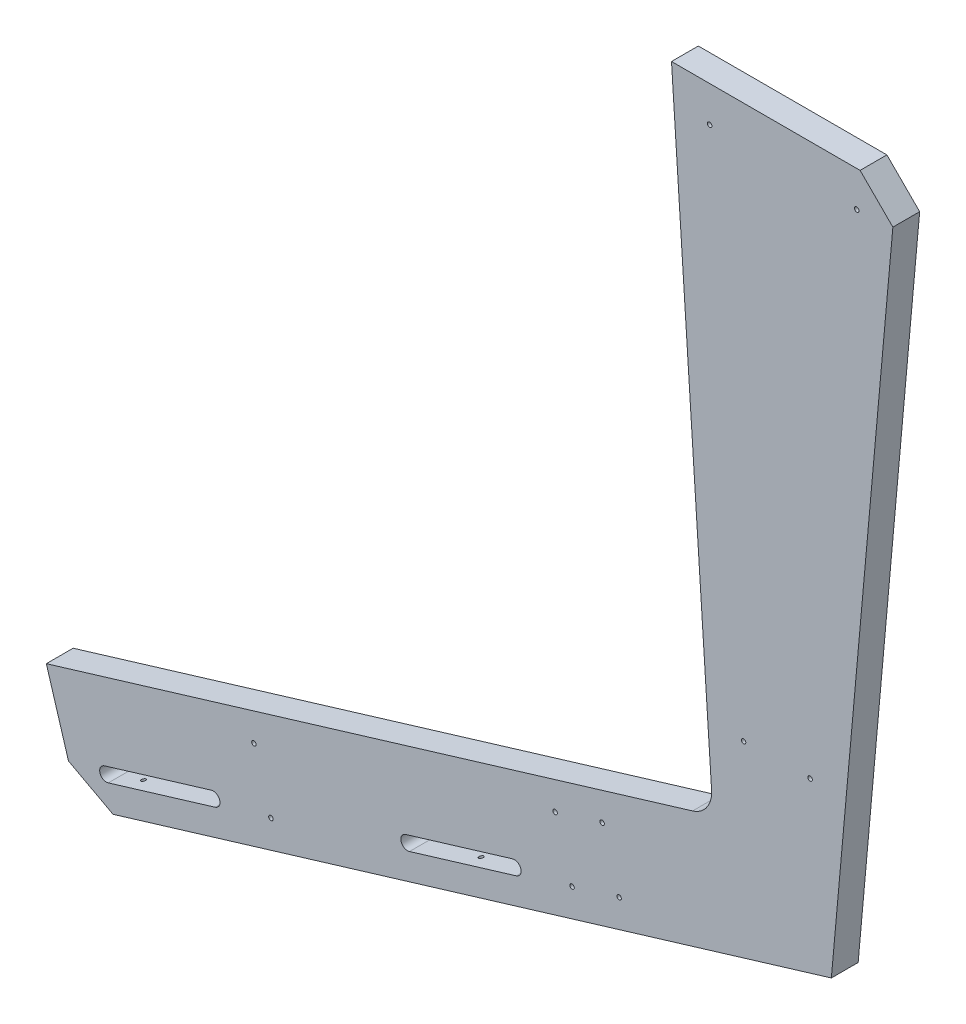
SolidWorks part; units mm, degrees
material "Beech"
ref_plane "Front Plane" through (0, 0, 0) normal (0, 0, 1) x (1, 0, 0)
ref_plane "Top Plane" through (0, 0, 0) normal (0, 1, 0) x (1, 0, 0)
ref_plane "Right Plane" through (0, 0, 0) normal (1, 0, 0) x (0, 0, -1)
sketch "Sketch1" plane through (0, 0, 0) normal (0, 0, 1) x (1, 0, 0)
  line L0 (-3.9531, 12.7) -> (24.5527, -421.626)
  line L1 (-3.9531, 12.7) -> (155.4923, 12.7)
  line L2 (155.4923, 12.7) -> (109.6671, -494.6316)
  line L6 (11.062, -441.1068) -> (-448.2883, -580.1316)
  line L7 (244.2135, 4.6862) -> (-115.2822, 37.1579) construction
  line L8 (-448.2883, -580.1316) -> (-425.1737, -656.504)
  line L11 (-425.1737, -656.504) -> (109.6671, -494.6316)
  arc A1 (24.5527, -421.626) -> (11.062, -441.1068) centre (5.5436, -422.8736) cw
  dimension "D3" = 22
  dimension "D2" = 19.05
  dimension "D1" = 509.397
  dimension "D4" = 79.7937
  dimension "D5" = 558.8
  dimension "D6" = 447.2969
extrude "Boss-Extrude1" add sketch "Sketch1" against normal blind 19.05
ref_plane "CL" through (0, 0, -9.525) normal (0, 0, 1) x (1, 0, 0)
chamfer "Chamfer1" distance 25.4 angle 45 2 edges at (-425.1737, -656.504, -9.525) (155.4923, 12.7, -9.525) first distance on face at (-157.7533, -575.5678, -9.525) first distance on face at (75.7696, 12.7, -9.525)
hole_wizard "3/8 Clearance Slot1" positions "Sketch18" profile "Sketch17" size "3/8" standard "ANSI Inch" slot yes end condition up to next
sketch "Sketch18" plane through (0, 0, 0) normal (0, 0, 1) x (1, 0, 0)
  line L0 (-196.1142, -563.5199) -> (-111.0259, -537.7675) construction
  line L1 (-400.8628, -649.1461) -> (109.6671, -494.6316) construction
  line L3 (11.062, -441.1068) -> (-448.2883, -580.1316) construction
  line L5 (-17.2403, 215.1482) -> (3.9976, -108.4402) construction
  line L7 (-3.9531, 12.7) -> (24.5527, -421.626) construction
  line L8 (-111.0259, -537.7675) -> (29.3862, -495.271) construction
  point P0 (-153.5701, -550.6437)
  point P24 (-367.628, -615.4294)
  dimension "D1" = 88.9
  dimension "D2" = 57.15
  dimension "D3" = 146.7021
  dimension "D4" = 223.647
sketch "Sketch17" plane through (-153.5701, -550.6437, 0) normal (1, 0, 0) x (0, -1, 0)
  line L0 (0, 0) -> (0, 19.05)
  line L1 (0, 19.05) -> (4.7625, 19.05)
  line L2 (4.7625, 19.05) -> (4.7625, 0)
  line L5 (4.7625, 0) -> (0, 0)
  line L11 (0, -6.35) -> (0, 107.95) construction
  dimension "Thru Hole Dia." = 9.525
  dimension "Thru Hole Depth" = 19.05
hole_wizard "Hole6" positions "Sketch19" profile "Sketch20" legacy
sketch "Sketch19" plane through (297.008, -457.8353, 165.475) normal (0.2897, -0.9571, 0) x (0, 0, 1)
  line L0 (-175, 310.0628) -> (-175, 724.4414) construction
  line L3 (-81.55, 824.9675) -> (-81.55, 609.9098) construction
  line L7 (-165.475, 600.3848) -> (0, 600.3848) construction
  line L9 (-175, 376.7378) -> (0, 376.7378) construction
  line L12 (0, 3.9184) -> (0, 227.5654) construction
  point P20 (-81.55, 717.4386)
  point P22 (-81.55, 641.6598)
  point P24 (-81.55, 793.2175)
  point P27 (-175, 705.3914)
  point P29 (-175, 329.1128)
  point P32 (-175, 579.9652)
  point P34 (-175, 454.539)
  point P35 (-175, 517.2521)
  point P50 (-127.375, 600.3848)
  point P52 (-38.1, 600.3848)
  point P61 (-127.375, 376.7378)
  point P63 (-38.1, 376.7378)
  point P74 (38.1, 376.7378)
  point P75 (127.375, 376.7378)
  point P76 (38.1, 600.3848)
  point P77 (127.375, 600.3848)
  point P78 (175, 517.2521)
  point P79 (175, 454.539)
  point P80 (175, 579.9652)
  point P81 (175, 329.1128)
  point P82 (175, 705.3914)
  point P83 (81.55, 793.2175)
  point P84 (81.55, 641.6598)
  point P85 (81.55, 717.4386)
sketch "Sketch20" plane through (-389.6698, -665.6619, 247.025) normal (0, 0, 1) x (0.9571, 0.2897, 0)
  line L0 (0, 0) -> (0, 39.0539)
  line L1 (0, 39.0539) -> (1.5875, 38.1)
  line L2 (1.5875, 38.1) -> (1.5875, 4.0177)
  line L3 (1.5875, 4.0177) -> (5.08, 0)
  line L4 (5.08, 0) -> (0, 0)
  line L5 (0, -14.3089) -> (0, 102.4216) construction
  line L6 (0, 39.0539) -> (-1.5875, 38.1) construction
  line L7 (-1.5875, 4.0177) -> (-5.08, 0) construction
  dimension "Diameter" = 3.175
  dimension "Depth" = 38.1
  dimension "C-Sink Diameter" = 10.16
  dimension "C-Sink Angle" = 82
  dimension "Drill Angle" = 118
hole_wizard "Hole7" positions "Sketch21" profile "Sketch22" legacy
sketch "Sketch21" plane through (155.2867, 10.4243, -19.05) normal (0, 0, -1) x (-0.09, -0.9959, 0)
  line L0 (9.7688, 133.4475) -> (528.1685, 52.1167) construction
  line L5 (0.0093, 25.4) -> (517.3743, 25.4) construction
  line L8 (660.1216, 540.8653) -> (441.5979, 0) construction
  line L11 (698.7793, 525.2466) -> (486.5659, 0) construction
  line L15 (604.5365, 403.2872) -> (643.1942, 387.6685) construction
  line L17 (520.7568, 195.9254) -> (559.4145, 180.3066) construction
  line L19 (507.6737, 163.5435) -> (546.3314, 147.9247) construction
  point P17 (34.8618, 129.5107)
  point P19 (398.7112, 72.427)
  point P22 (25.4093, 25.4)
  point P24 (393.7093, 25.4)
  point P40 (604.5365, 403.2872)
  point P41 (643.1942, 387.6685)
  point P44 (520.7568, 195.9254)
  point P45 (559.4145, 180.3066)
  point P48 (507.6737, 163.5435)
  point P49 (546.3314, 147.9247)
sketch "Sketch22" plane through (-41.186, -520.3847, -19.05) normal (1, 0, 0) x (0, 1, 0)
  line L0 (0, 0) -> (0, 40.64)
  line L1 (0, 40.64) -> (1.5875, 39.6861)
  line L2 (1.5875, 39.6861) -> (1.5875, 4.0177)
  line L3 (1.5875, 4.0177) -> (5.08, 0)
  line L4 (5.08, 0) -> (0, 0)
  line L5 (0, -14.3089) -> (0, 102.4216) construction
  line L6 (0, 40.64) -> (-1.5875, 39.6861) construction
  line L7 (-1.5875, 4.0177) -> (-5.08, 0) construction
  dimension "Diameter" = 3.175
  dimension "Depth" = 40.64
  dimension "C-Sink Diameter" = 10.16
  dimension "C-Sink Angle" = 82
  dimension "Drill Angle" = 118
